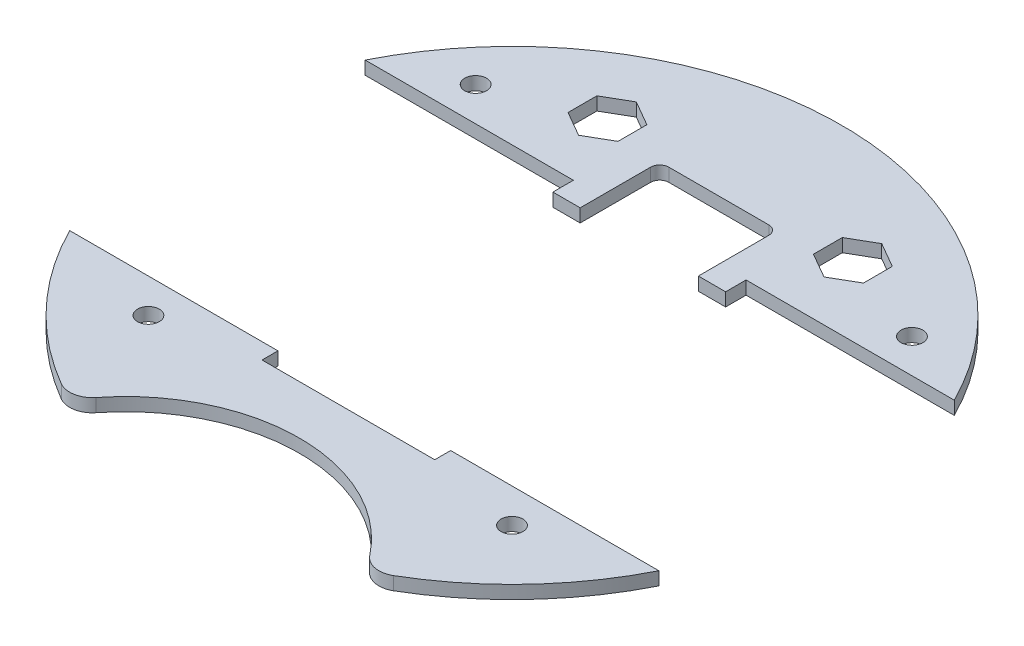
SolidWorks part; units mm, degrees
material "Acrylic (Medium-high impact)"
ref_plane "Front Plane" through (0, 0, 0) normal (0, 0, 1) x (1, 0, 0)
ref_plane "Top Plane" through (0, 0, 0) normal (0, 1, 0) x (1, 0, 0)
ref_plane "Right Plane" through (0, 0, 0) normal (1, 0, 0) x (0, 0, -1)
sketch "Sketch1" plane through (0, 0, 0) normal (0, 1, 0) x (1, 0, 0)
  line L0 (0, -85) -> (-32.4891, -64.8129) construction
  line L1 (0, -85) -> (0, 0) construction
  arc A0 (36.5434, -62.6165) -> (-36.5434, -62.6165) centre (0, 0) ccw
  arc A1 (30.0898, -61.3851) -> (-30.0898, -61.3851) centre (0, -85) ccw
  arc A2 (36.5434, -62.6165) -> (30.0898, -61.3851) centre (34.0231, -58.2982) cw
  arc A3 (-30.0898, -61.3851) -> (-36.5434, -62.6165) centre (-34.0231, -58.2982) cw
  dimension "D1" = 145
  dimension "D2" = 76.5
  dimension "D4" = 5
  dimension "D3" = 85
extrude "Boss-Extrude1" add sketch "Sketch1" along normal blind 2.9
sketch "solenoid placement" plane through (0, 2.9, 0) normal (0, 1, 0) x (1, 0, 0)
  line L4 (-19, -36) -> (19, -36)
  line L5 (-19, 28) -> (-19, -36)
  line L6 (19, 28) -> (-19, 28)
  line L7 (19, -36) -> (19, 28)
  line L8 (-19, -36) -> (19, -36)
  line L9 (-19, 28) -> (-19, -36)
  line L10 (19, 28) -> (-19, 28)
  line L11 (19, -36) -> (19, 28)
  dimension "D1" = 0
extrude "Cut-Extrude1" cut sketch "solenoid placement" against normal through all
sketch "Sketch5" plane through (0, 2.9, 0) normal (0, 1, 0) x (1, 0, 0)
  line L12 (-21.5, 51.1754) -> (-27, 54.3509)
  line L13 (-27, 54.3509) -> (-32.5, 51.1754)
  line L14 (-32.5, 51.1754) -> (-32.5, 44.8246)
  line L15 (-32.5, 44.8246) -> (-27, 41.6491)
  line L16 (-27, 41.6491) -> (-21.5, 44.8246)
  line L17 (-21.5, 44.8246) -> (-21.5, 51.1754)
  line L18 (-21.5, 51.1754) -> (-27, 54.3509)
  line L19 (-27, 54.3509) -> (-32.5, 51.1754)
  line L20 (-32.5, 51.1754) -> (-32.5, 44.8246)
  line L21 (-32.5, 44.8246) -> (-27, 41.6491)
  line L22 (-27, 41.6491) -> (-21.5, 44.8246)
  line L23 (-21.5, 44.8246) -> (-21.5, 51.1754)
  line L24 (21.5, 51.1754) -> (21.5, 44.8246)
  line L25 (21.5, 44.8246) -> (27, 41.6491)
  line L26 (27, 41.6491) -> (32.5, 44.8246)
  line L27 (32.5, 44.8246) -> (32.5, 51.1754)
  line L28 (32.5, 51.1754) -> (27, 54.3509)
  line L29 (27, 54.3509) -> (21.5, 51.1754)
  line L30 (21.5, 51.1754) -> (21.5, 44.8246)
  line L31 (21.5, 44.8246) -> (27, 41.6491)
  line L32 (27, 41.6491) -> (32.5, 44.8246)
  line L33 (32.5, 44.8246) -> (32.5, 51.1754)
  line L34 (32.5, 51.1754) -> (27, 54.3509)
  line L35 (27, 54.3509) -> (21.5, 51.1754)
  dimension "D1" = 0
  dimension "D2" = 0
extrude "Cut-Extrude5" cut sketch "Sketch5" against normal through all
sketch "Sketch6" plane through (0, 2.9, 0) normal (0, 1, 0) x (1, 0, 0)
  circle A1 centre (40, -40) radius 2.4
  circle A2 centre (40, -40) radius 2.4
  circle A3 centre (-40, -40) radius 2.4
  circle A4 centre (-40, -40) radius 2.4
  circle A5 centre (48, 40) radius 2.4
  circle A6 centre (48, 40) radius 2.4
  circle A7 centre (-48, 40) radius 2.4
  circle A8 centre (-48, 40) radius 2.4
  dimension "D1" = 0
  dimension "D2" = 0
  dimension "D3" = 0
  dimension "D4" = 0
extrude "Cut-Extrude6" cut sketch "Sketch6" against normal through all
sketch "Sketch3" plane through (0, 2.9, 0) normal (0, 1, 0) x (1, 0, 0)
  line L0 (-19, 28) -> (-19, 32.5)
  line L1 (72.5, -32.5) -> (-72.5, -32.5)
  line L2 (72.5, -32.5) -> (72.5, 32.5)
  line L3 (72.5, 32.5) -> (19, 32.5)
  line L4 (-72.5, -32.5) -> (-72.5, 32.5)
  line L5 (72.5, -32.5) -> (-72.5, 32.5) construction
  line L6 (72.5, 32.5) -> (-72.5, -32.5) construction
  line L7 (-19, 28) -> (19, 28)
  line L8 (19, 28) -> (19, 32.5)
  line L9 (-19, 32.5) -> (-72.5, 32.5)
  arc A0 (36.5434, -62.6165) -> (-36.5434, -62.6165) centre (0, 0) ccw construction
  point P0 (0, 0)
  dimension "D1" = 65
extrude "Cut-Extrude3" cut sketch "Sketch3" against normal through all
sketch "Sketch7" plane through (0, 2.9, 0) normal (0, 1, 0) x (1, 0, 0)
  line L8 (13, 28) -> (13, 43.5)
  line L9 (-13, 28) -> (13, 28)
  line L10 (-13, 43.5) -> (-13, 28)
  line L11 (11, 45.5) -> (-11, 45.5)
  line L20 (13, 28) -> (13, 43.5)
  line L21 (-13, 28) -> (13, 28)
  line L22 (-13, 43.5) -> (-13, 28)
  line L23 (11, 45.5) -> (-11, 45.5)
  arc A4 (-11, 45.5) -> (-13, 43.5) centre (-11, 43.5) ccw
  arc A5 (13, 43.5) -> (11, 45.5) centre (11, 43.5) ccw
  arc A10 (-11, 45.5) -> (-13, 43.5) centre (-11, 43.5) ccw
  arc A11 (13, 43.5) -> (11, 45.5) centre (11, 43.5) ccw
  dimension "D1" = 0
extrude "Cut-Extrude7" cut sketch "Sketch7" against normal through all
equation "\"smallPulleyTeeth\"= 15"
equation "\"largePulleyTeeth\"= 30"
equation "\"eighthThick\"= 2.9mm"
equation "\"sixteenthThick\" = 1.7mm"
equation "\"quarterThick\"=6.0mm"
equation "\"OD\" = 145mm"
equation "\"puckAngle\" = 60.5deg"
equation "\"D1@Sketch1\"=\"OD\""
equation "\"puckDiam\" = 76.5mm"
equation "\"D2@Sketch1\"=\"puckDiam\""
equation "\"D1@Boss-Extrude1\"=\"eighthThick\""
equation "\"axlePress\" = 5.9mm"
equation "\"press\" = 0.2mm"
equation "\"wheelClear\" = 0.3mm"
equation "\"10-32clear\" = 4.8mm"
equation "\"6-32clear\" = 3.3mm"
equation "\"8-32clear\" = 4.0mm"
equation "\"wheelHeight\" = 22mm"
equation "\"wheelWell\" = 65mm"
equation "\"D1@Sketch3\"=\"wheelWell\""
equation "\"puckDist\" = 85mm"
equation "\"scoopFillet\" = 5mm"
equation "\"4-40clear\" = 3.0mm"
equation "\"D3@Sketch1\"=\"puckDist\""
equation "\"D4@Sketch1\"=\"scoopFillet\""
